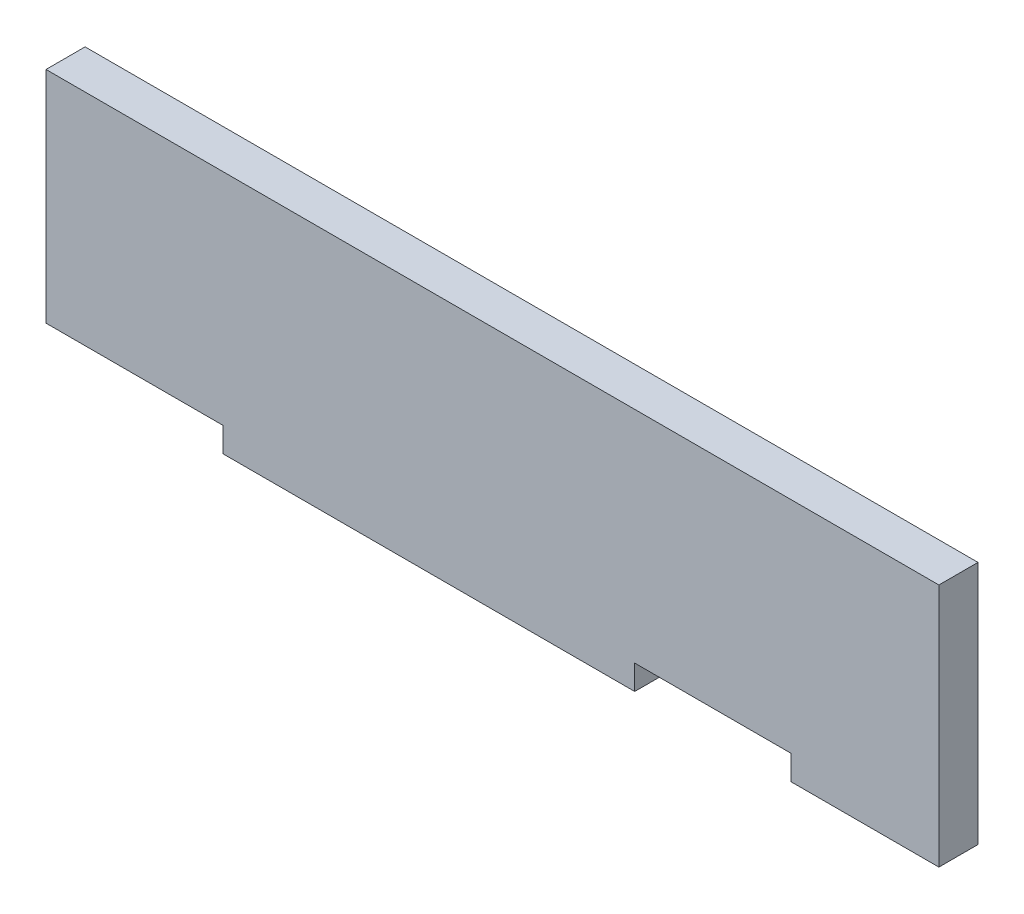
SolidWorks part; units mm, degrees
ref_plane "Front Plane" through (0, 0, 0) normal (0, 0, 1) x (1, 0, 0)
ref_plane "Top Plane" through (0, 0, 0) normal (0, 1, 0) x (1, 0, 0)
ref_plane "Right Plane" through (0, 0, 0) normal (1, 0, 0) x (0, 0, -1)
sketch "Sketch1" plane through (0, 0, 0) normal (0, 0, 1) x (1, 0, 0)
  line L1 (300, 0) -> (-135, 0)
  line L2 (300, 0) -> (300, 119.05)
  line L3 (300, 119.05) -> (-135, 119.05)
  line L4 (-135, 0) -> (-135, 119.05)
  line L5 (-300, 119.05) -> (300, 119.05) construction
  dimension "D1" = 119.05
  dimension "D2" = 435
extrude "Boss-Extrude1" add sketch "Sketch1" along normal blind 19.05
sketch "Sketch2" plane through (0, 0, 19.05) normal (0, 0, 1) x (1, 0, 0)
  line L1 (-48.8, 12) -> (-125, 12) construction
  line L2 (-48.8, 0) -> (-48.8, 12) construction
  line L3 (-135, 0) -> (300, 0) construction
  line L4 (151.8, 0) -> (151.8, 12) construction
  line L5 (151.8, 12) -> (228, 12) construction
  line L6 (228, 12) -> (228, 0) construction
  line L8 (-48.8, 12) -> (-125, 12)
  line L9 (-48.8, 0) -> (-48.8, 12)
  line L10 (-125, 0) -> (-48.8, 0)
  line L11 (151.8, 0) -> (151.8, 12)
  line L12 (151.8, 12) -> (228, 12)
  line L13 (228, 12) -> (228, 0)
  line L14 (151.8, 0) -> (228, 0)
  line L15 (-125, 12) -> (-135, 12)
  line L16 (-135, 119.05) -> (-135, 0) construction
  line L17 (-135, 12) -> (-135, 0)
  line L18 (-135, 0) -> (-125, 0)
extrude "Cut-Extrude1" cut sketch "Sketch2" against normal through all
